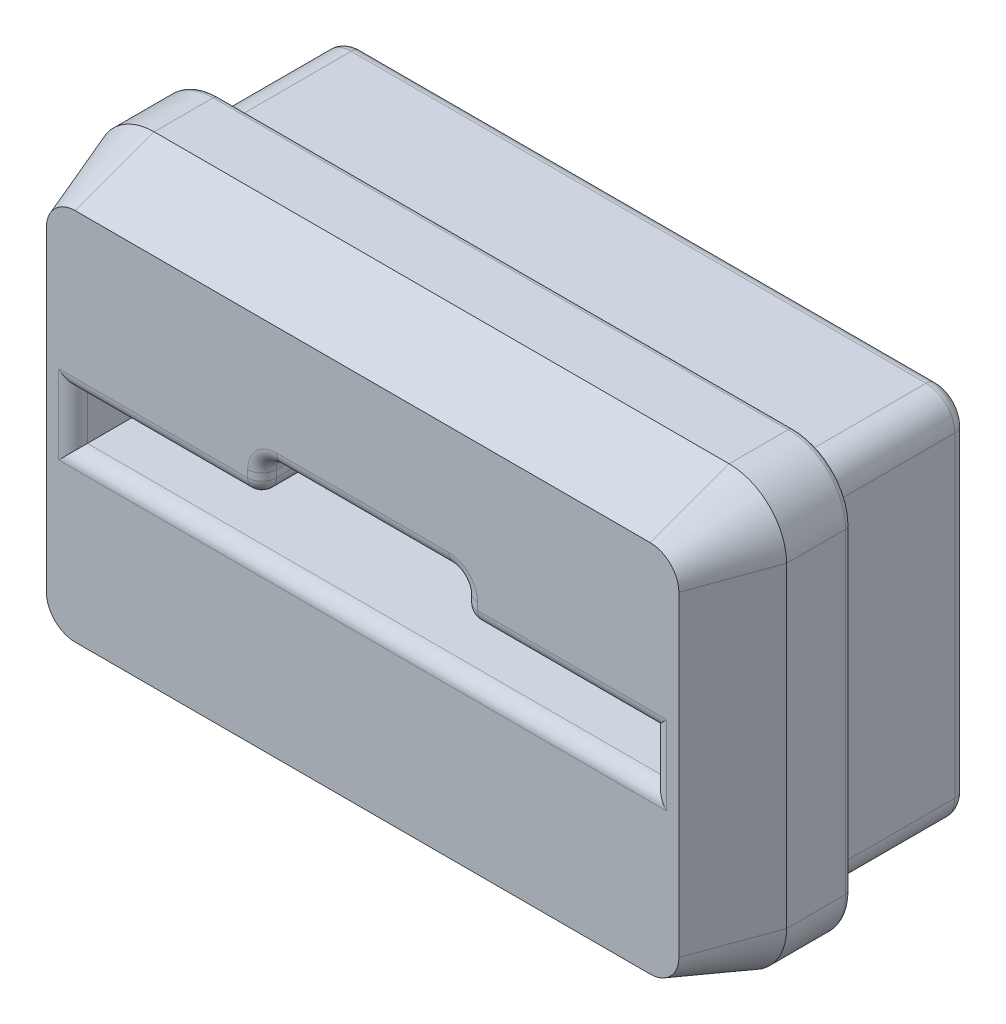
SolidWorks part; units mm, degrees
ref_plane "Front Plane" through (0, 0, 0) normal (0, 0, 1) x (1, 0, 0)
ref_plane "Top Plane" through (0, 0, 0) normal (0, 1, 0) x (1, 0, 0)
ref_plane "Right Plane" through (0, 0, 0) normal (1, 0, 0) x (0, 0, -1)
sketch "Sketch1" plane through (0, 0, 0) normal (0, 1, 0) x (1, 0, 0)
  line L1 (-12, 6.5) -> (12, 6.5)
  line L2 (-12, 6.5) -> (-12, -6.5)
  line L3 (-12, -6.5) -> (12, -6.5)
  line L4 (12, 6.5) -> (12, -6.5)
  line L5 (-12, 6.5) -> (12, -6.5) construction
  line L6 (-12, -6.5) -> (12, 6.5) construction
  point P0 (0, 0)
  dimension "D1" = 24
  dimension "D2" = 13
extrude "Boss-Extrude1" add sketch "Sketch1" along normal blind 15
sketch "Sketch2" plane through (0, 0, 6.5) normal (0, 0, 1) x (1, 0, 0)
  line L0 (0, 0) -> (0, 15) construction
  line L1 (-12, 15) -> (12, 15) construction
  line L2 (-12, 0) -> (12, 0) construction
  line L3 (-10.075, 8.45) -> (10.075, 8.45)
  line L4 (-10.075, 8.45) -> (-10.075, 6.7)
  line L5 (-10.075, 6.7) -> (10.075, 6.7)
  line L6 (10.075, 8.45) -> (10.075, 6.7)
  line L7 (-10.075, 8.45) -> (10.075, 6.7) construction
  line L8 (-10.075, 6.7) -> (10.075, 8.45) construction
  point P5 (0, 7.575)
  dimension "D1" = 6.7
  dimension "D2" = 1.75
  dimension "D3" = 20.15
extrude "Cut-Extrude1" cut sketch "Sketch2" against normal blind 15
fillet "Fillet1" radius 2 4 edges at (12, 15, 0) (12, 0, 0) (-12, 0, 0) (-12, 15, 0)
chamfer "Chamfer2" distance 1 angle 70 8 edges at (0, 0, 6.5) (-11.4142, 0.5858, 6.5) (11.4142, 0.5858, 6.5) (-12, 7.5, 6.5) (12, 7.5, 6.5) (-11.4142, 14.4142, 6.5) (11.4142, 14.4142, 6.5) (0, 15, 6.5) first distance on face at (0, 7.575, 6.5)
fillet "Fillet2" radius 0.5 4 edges at (10.075, 7.575, 6.5) (0, 8.45, 6.5) (-10.075, 7.575, 6.5) (0, 6.7, 6.5)
sketch "Sketch4" plane through (0, 0, -6.5) normal (0, 0, -1) x (-1, 0, 0)
  line L0 (-10.075, 8.45) -> (-8.575, 8.45)
  line L1 (-10.075, 6.7) -> (10.075, 6.7)
  line L2 (-10.075, 6.7) -> (-10.075, 8.45)
  line L3 (-8.575, 11.8912) -> (8.575, 11.8912)
  line L4 (10.075, 6.7) -> (10.075, 8.45)
  line L5 (-10.075, 8.45) -> (10.075, 8.45) construction
  line L6 (-8.575, 8.45) -> (-8.575, 11.8912)
  line L7 (10.075, 8.45) -> (8.575, 8.45)
  line L8 (8.575, 8.45) -> (8.575, 11.8912)
  dimension "D2" = 1.5
  dimension "D3" = 1.5
extrude "Cut-Extrude4" cut sketch "Sketch4" against normal blind 11
sketch "Sketch5" plane through (0, 0, -6.5) normal (0, 0, -1) x (-1, 0, 0)
  line L5 (-13.5112, 17.4159) -> (13.3444, 17.4159)
  line L6 (-13.5112, 17.4159) -> (-13.5112, -1.8918)
  line L7 (-13.5112, -1.8918) -> (13.3444, -1.8918)
  line L8 (10, 14) -> (-10, 14)
  line L9 (-11, 13) -> (-11, 2)
  line L10 (-10, 1) -> (10, 1)
  line L11 (11, 2) -> (11, 13)
  line L12 (10, 14) -> (-10, 14)
  line L13 (-11, 13) -> (-11, 2)
  line L14 (-10, 1) -> (10, 1)
  line L15 (11, 2) -> (11, 13)
  line L16 (13.3444, 17.4159) -> (13.3444, -1.8918)
  arc A8 (-10, 14) -> (-11, 13) centre (-10, 13) ccw
  arc A9 (-11, 2) -> (-10, 1) centre (-10, 2) ccw
  arc A10 (10, 1) -> (11, 2) centre (10, 2) ccw
  arc A11 (11, 13) -> (10, 14) centre (10, 13) ccw
  arc A12 (-10, 14) -> (-11, 13) centre (-10, 13) ccw
  arc A13 (-11, 2) -> (-10, 1) centre (-10, 2) ccw
  arc A14 (10, 1) -> (11, 2) centre (10, 2) ccw
  arc A15 (11, 13) -> (10, 14) centre (10, 13) ccw
  dimension "D1" = 1
extrude "Cut-Extrude5" cut sketch "Sketch5" against normal blind 8
sketch "Sketch6" plane through (0, 0, -6.5) normal (0, 0, -1) x (-1, 0, 0)
  line L8 (-9, 5.7) -> (9, 5.7)
  line L9 (10.075, 6.7) -> (-10.075, 6.7) construction
  line L12 (10, 13) -> (-10, 13)
  line L13 (-10, 13) -> (-10, 2)
  line L14 (-10, 2) -> (10, 2)
  line L15 (10, 2) -> (10, 13)
  line L17 (-10, 4.7) -> (-10, 3)
  line L18 (-9, 2) -> (9, 2)
  line L19 (10, 3) -> (10, 4.7)
  arc A8 (9, 2) -> (10, 3) centre (9, 3) ccw
  arc A9 (9, 5.7) -> (10, 4.7) centre (9, 4.7) cw
  arc A10 (-10, 3) -> (-9, 2) centre (-9, 3) ccw
  arc A11 (-9, 5.7) -> (-10, 4.7) centre (-9, 4.7) ccw
  dimension "D3" = 1
  dimension "D2" = 1
  dimension "D1" = 1
extrude "Cut-Extrude6" cut sketch "Sketch6" against normal blind 11
sketch "Sketch7" plane through (0, 0, -6.5) normal (0, 0, -1) x (-1, 0, 0)
  line L1 (-14.3755, 18.0591) -> (15.6072, 18.0591)
  line L2 (-14.3755, 18.0591) -> (-14.3755, -3.4999)
  line L3 (-14.3755, -3.4999) -> (15.6072, -3.4999)
  line L4 (15.6072, 18.0591) -> (15.6072, -3.4999)
extrude "Cut-Extrude7" cut sketch "Sketch7" against normal blind 3
chamfer "Chamfer3" distance 2 angle 45 2 edges at (9.325, 8.45, -3.5) (-9.325, 8.45, -3.5)
fillet "Fillet3" radius 0.4 22 edges at (-9.7071, 5.4071, -3.5) (0, 5.7, -3.5) (9.7071, 5.4071, -3.5) (10, 3.85, -3.5) (9.7071, 2.2929, -3.5) (0, 2, -3.5) (-9.7071, 2.2929, -3.5) (10.7071, 13.7071, -3.5) (11, 7.5, -3.5) (10.7071, 1.2929, -3.5) (0, 1, -3.5) (-10.7071, 1.2929, -3.5) (-11, 7.5, -3.5) (-10.7071, 13.7071, -3.5) (9.325, 10.45, -3.5) (8.575, 11.1706, -3.5) (-9.325, 10.45, -3.5) (-8.575, 11.1706, -3.5) (0, 11.8912, -3.5) (0, 6.7, -3.5) (-10, 3.85, -3.5) (0, 14, -3.5)
fillet "Fillet4" radius 0.2 8 edges at (0, 15, 1.5) (11.4142, 14.4142, 1.5) (12, 7.5, 1.5) (11.4142, 0.5858, 1.5) (0, 0, 1.5) (-11.4142, 0.5858, 1.5) (-12, 7.5, 1.5) (-11.4142, 14.4142, 1.5)
sketch "Sketch8" plane through (0, 0, 4.5) normal (0, 0, -1) x (-1, 0, 0)
  line L0 (8.575, 8.45) -> (-8.575, 8.45) construction
  line L1 (-3.5, 9.7) -> (3.5, 9.7)
  line L2 (-3.5, 9.7) -> (-3.5, 7.2)
  line L3 (-3.5, 7.2) -> (3.5, 7.2)
  line L4 (3.5, 9.7) -> (3.5, 7.2)
  line L5 (-3.5, 9.7) -> (3.5, 7.2) construction
  line L6 (-3.5, 7.2) -> (3.5, 9.7) construction
  point P0 (0, 8.45)
  dimension "D1" = 2.5
  dimension "D2" = 7
extrude "Cut-Extrude8" cut sketch "Sketch8" against normal through all
fillet "Fillet5" radius 0.5 9 edges at (3.5, 8.45, 5.25) (3.5, 8.5964, 6.3536) (3.5, 9.325, 6.5) (0, 9.7, 6.5) (-3.5, 9.325, 6.5) (-3.5, 8.45, 5.25) (-3.5, 8.5964, 6.3536) (-3.5, 9.7, 5.5) (3.5, 9.7, 5.5)
